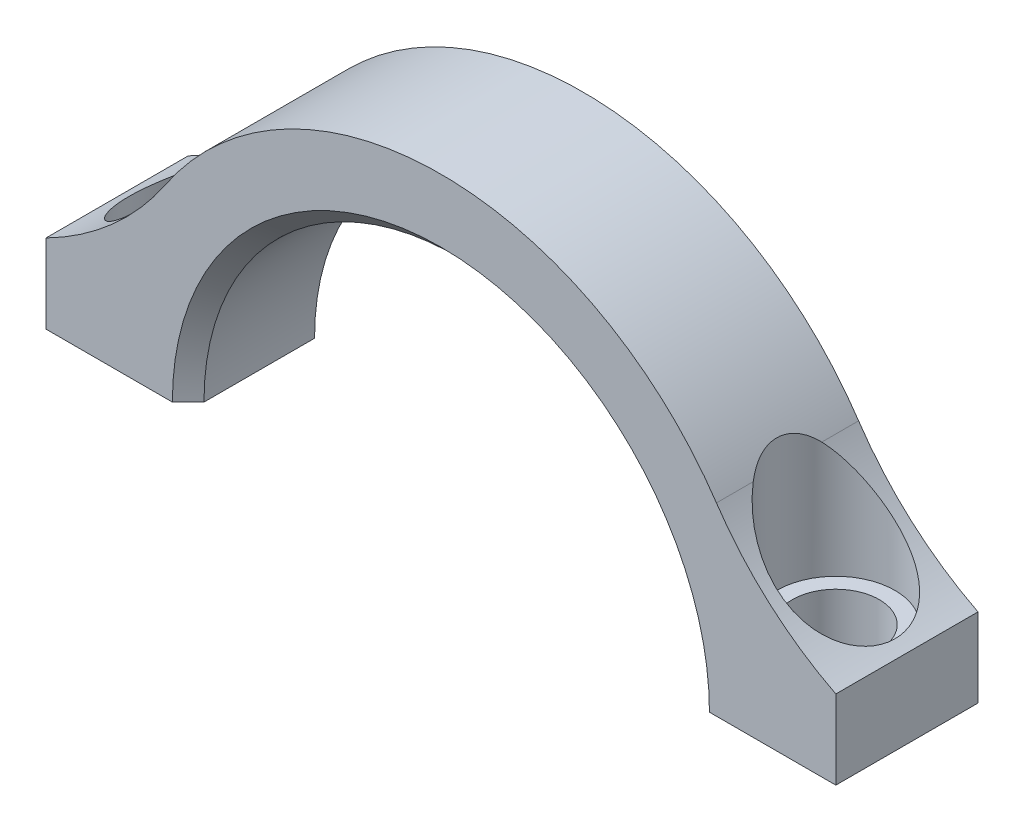
SolidWorks part; units mm, degrees
ref_plane "Alzado" through (0, 0, 0) normal (0, 0, 1) x (1, 0, 0)
ref_plane "Planta" through (0, 0, 0) normal (0, 1, 0) x (1, 0, 0)
ref_plane "Vista lateral" through (0, 0, 0) normal (1, 0, 0) x (0, 0, -1)
sketch "Croquis1" plane through (0, 0, 0) normal (0, 0, 1) x (1, 0, 0)
  line L0 (32, 0) -> (50, 0)
  line L1 (-32, 0) -> (-50, 0)
  line L2 (-50, 0) -> (-50, 10)
  line L3 (-50, 10) -> (-40.7922, 10)
  line L4 (50, 0) -> (50, 10)
  line L5 (50, 10) -> (40.7922, 10)
  arc A0 (32, 0) -> (-32, 0) centre (0, 0) ccw
  arc A1 (40.7922, 10) -> (-40.7922, 10) centre (0, 0) ccw
  dimension "D1" = 64
  dimension "D3" = 10
  dimension "D2" = 18
  dimension "D4" = 18
  dimension "D5" = 10
  dimension "D6" = 10
extrude "Saliente-Extruir1" add sketch "Croquis1" along normal blind 18
ref_plane "Plano1" through (0, 10, 0) normal (0, 1, 0) x (1, 0, 0)
sketch "Croquis2" plane through (0, 10, 0) normal (0, 1, 0) x (1, 0, 0)
  line L0 (32, -18) -> (50, -18) construction
  line L1 (32, -18) -> (50, -18) construction
  line L2 (32, -18) -> (50, 0) construction
  circle A0 centre (41, -9) radius 7.5
  point P2 (41, -9)
  dimension "D1" = 15
extrude "Cortar-Extruir1" cut sketch "Croquis2" along normal blind 36
mirror "Simetría1" about plane through (0, 0, 0) normal (1, 0, 0) of "Cortar-Extruir1"
sketch "Croquis3" plane through (0, 10, 0) normal (0, 1, 0) x (1, 0, 0)
  line L0 (-32, -18) -> (-50, 0) construction
  line L2 (-40.7922, -18) -> (-50, -18) construction
  point P3 (-45.4943, -70.1255)
  point P8 (-41, -9)
hole_wizard "Refrentado para perno con cabeza hexagonal (calidades AB) de M21" positions "Croquis3D1" profile "Croquis8" counterbore size "M2" standard "AS"
sketch3d "Croquis3D1"
  point P0 (-41, 10, 9)
  point P3 (41, 10, 9)
sketch "Croquis8" plane through (-41, 10, 9) normal (1, 0, 0) x (0, 0, 1)
  line L0 (0, 0) -> (0, 43.3047)
  line L1 (0, 43.3047) -> (5.5, 40)
  line L2 (5.5, 40) -> (5.5, 1.4)
  line L3 (5.5, 1.4) -> (7.5, 1.4)
  line L4 (7.5, 1.4) -> (7.5, 0)
  line L5 (7.5, 0) -> (0, 0)
  line L10 (0, 43.3047) -> (-5.5, 40) construction
  line L11 (0, -6.35) -> (0, 107.95) construction
  dimension "Diámetro de taladro" = 11
  dimension "Profundidad de taladro" = 40
  dimension "Diámetro de refrentado" = 15
  dimension "Profundidad de refrentado" = 1.4
  dimension "Ángulo de perforador" = 118
fillet "Redondeo1" radius 40 2 edges at (-40.7922, 10, 17.2486) (40.7922, 10, 17.2486)
chamfer "Chaflán1" distance 2 angle 45 2 edges at (0, 32, 18) (0, 32, 0)
